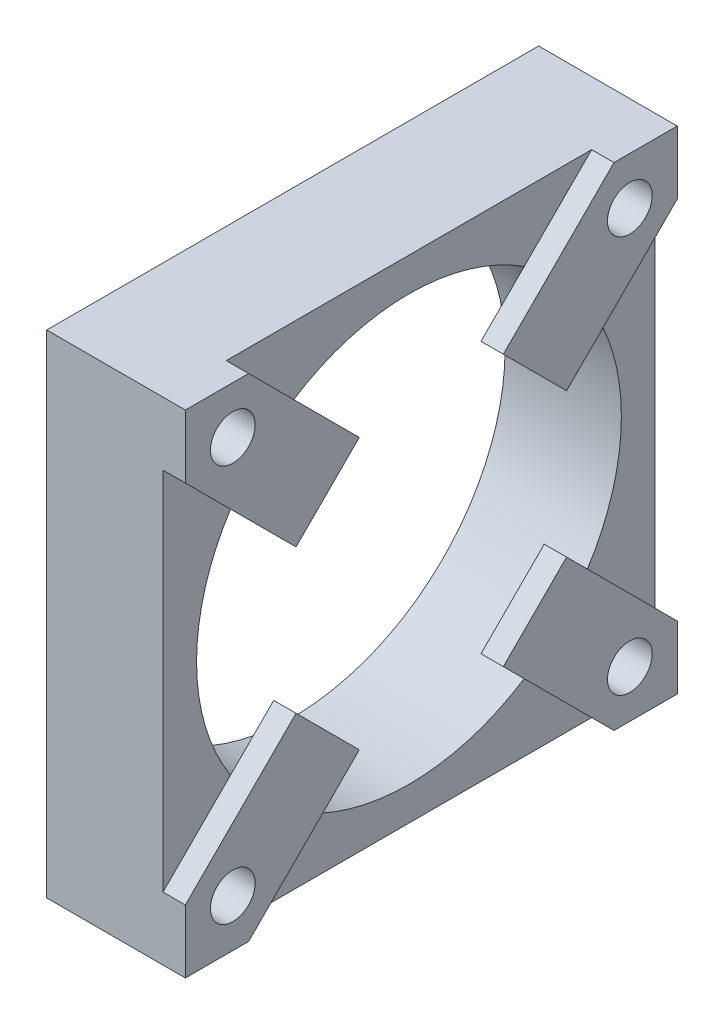
SolidWorks part; units mm, degrees
ref_plane "Front Plane" through (0, 0, 0) normal (0, 0, 1) x (1, 0, 0)
ref_plane "Top Plane" through (0, 0, 0) normal (0, 1, 0) x (1, 0, 0)
ref_plane "Right Plane" through (0, 0, 0) normal (1, 0, 0) x (0, 0, -1)
sketch "Sketch1" plane through (0, 0, 0) normal (1, 0, 0) x (0, 0, -1)
  line L1 (-27.94, 27.94) -> (27.94, 27.94)
  line L2 (-27.94, 27.94) -> (-27.94, -27.94)
  line L3 (-27.94, -27.94) -> (27.94, -27.94)
  line L4 (27.94, 27.94) -> (27.94, -27.94)
  line L5 (-27.94, 27.94) -> (27.94, -27.94) construction
  line L6 (-27.94, -27.94) -> (27.94, 27.94) construction
  circle A0 centre (0, 0) radius 24.13
  point P0 (0, 0)
  dimension "D1" = 48.26
  dimension "D2" = 55.88
  dimension "D3" = 55.88
extrude "Boss-Extrude1" add sketch "Sketch1" along normal blind 13.208
sketch "Sketch2" plane through (13.208, 0, 0) normal (1, 0, 0) x (0, 0, -1)
  line L0 (-27.94, 20.7558) -> (-27.94, 27.94)
  line L2 (-27.94, 27.94) -> (-20.7558, 27.94)
  line L3 (27.94, 27.94) -> (-27.94, 27.94) construction
  line L4 (-27.94, 27.94) -> (0, 0) construction
  line L5 (-27.94, 20.7558) -> (-15.3676, 8.1834)
  line L6 (-20.7558, 27.94) -> (-8.1834, 15.3676)
  line L7 (-15.3676, 8.1834) -> (-8.1834, 15.3676)
  line L8 (-24.3479, 31.5321) -> (3.5921, 3.5921) construction
  line L9 (-31.5321, 24.3479) -> (-3.5921, -3.5921) construction
  dimension "D3" = 22.86
  dimension "D1" = 5.08
  dimension "D2" = 5.08
extrude "Boss-Extrude2" add sketch "Sketch2" along normal blind 2.54
pattern_circular "CirPattern1" count 4 over 360 about axis through (13.208, 0, 0) along (1, 0, 0) of "Boss-Extrude2"
sketch "Sketch5" plane through (0, 0, 0) normal (1, 0, 0) x (0, 0, -1)
  line L0 (-27.94, -27.94) -> (0, 0) construction
  circle A0 centre (-22.5518, -22.5518) radius 2.54
  circle A1 centre (-22.5518, 22.5518) radius 2.54
  circle A2 centre (22.5518, 22.5518) radius 2.54
  circle A3 centre (22.5518, -22.5518) radius 2.54
  point P15 (0, 0)
  dimension "D1" = 5.08
  dimension "D2" = 7.62
  dimension "D3" = 4
extrude "Cut-Extrude2" cut sketch "Sketch5" against normal through all and the other way through all
